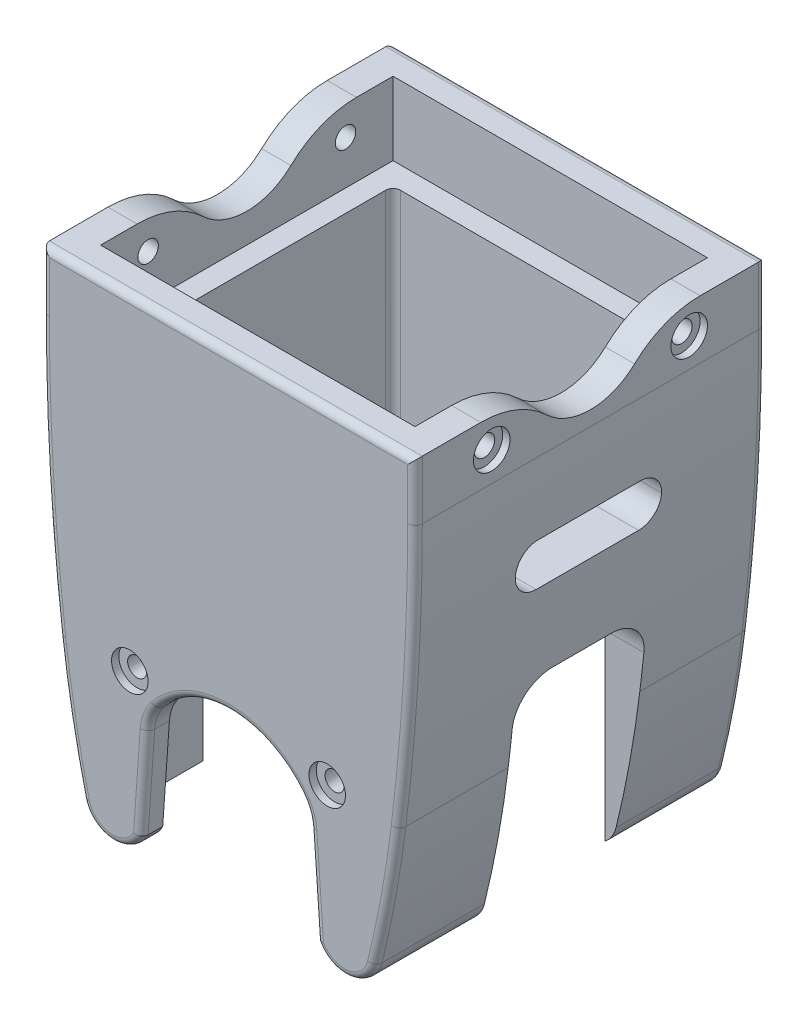
SolidWorks part; units mm, degrees
ref_plane "Front Plane" through (0, 0, 0) normal (0, 0, 1) x (1, 0, 0)
ref_plane "Top Plane" through (0, 0, 0) normal (0, 1, 0) x (1, 0, 0)
ref_plane "Right Plane" through (0, 0, 0) normal (1, 0, 0) x (0, 0, -1)
sketch "Sketch1" plane through (0, 0, 0) normal (0, 0, 1) x (1, 0, 0)
  line L0 (0, 18.8617) -> (0, -23.7037) construction
  line L1 (-12, -44.7495) -> (-11.0833, -31.7495)
  line L2 (-25.5, 18.8617) -> (0, 18.8617)
  line L7 (-25.5, 10.8617) -> (-25.5, 18.8617)
  line L10 (25.5, 10.8617) -> (25.5, 18.8617)
  line L11 (25.5, 18.8617) -> (0, 18.8617)
  line L12 (-16.2969, -47.1383) -> (16.2969, -47.1383) construction
  line L13 (11.0833, -31.7495) -> (12, -44.7495)
  arc A3 (-23.25, -26.1383) -> (-25.5, 10.8617) centre (279.8472, 10.8617) cw
  circle A14 centre (-13.5, -25.5854) radius 1.3
  arc A19 (23.25, -26.1383) -> (25.5, 10.8617) centre (-279.8472, 10.8617) ccw
  circle A20 centre (13.5, -25.5854) radius 1.3
  arc A21 (9.8042, -28.4495) -> (-9.8042, -28.4495) centre (0, -36.2037) ccw
  arc A22 (9.8042, -28.4495) -> (11.0833, -31.7495) centre (5.0982, -32.1715) cw
  arc A23 (-11.0833, -31.7495) -> (-9.8042, -28.4495) centre (-5.0982, -32.1715) cw
  arc A24 (-12, -44.7495) -> (-20, -43.9047) centre (-15.8479, -42.8869) cw
  arc A25 (-20, -43.9047) -> (-23.25, -26.1383) centre (127.6048, -7.723) cw
  arc A26 (20, -43.9047) -> (23.25, -26.1383) centre (-127.6048, -7.723) ccw
  arc A27 (12, -44.7495) -> (20, -43.9047) centre (15.8479, -42.8869) ccw
  point P2 (0, -23.7037)
  point P4 (0, 0)
  point P8 (0, 0)
  point P11 (-12.75, 18.8617)
  point P20 (-16.2969, -47.1383)
  point P34 (16.2969, -47.1383)
  dimension "D5" = 40
  dimension "D6" = 51
  dimension "D2" = 2.6
  dimension "D3" = 13
  dimension "D9" = 18.8617
  dimension "D10" = 6
  dimension "D11" = 31.6958
  dimension "D12" = 8
  dimension "D13" = 12.5
  dimension "D14" = 37
  dimension "D1" = 27
  dimension "D4" = 66
  dimension "D7" = 8
  dimension "D8" = 3.3
  dimension "D15" = 2.25
  dimension "D16" = 1.8817
extrude "Main Shape" add sketch "Sketch1" against normal mid plane 48
sketch "Sketch8" plane through (0, 0, 24) normal (0, 0, 1) x (1, 0, 0)
  circle A0 centre (-13.5, -25.5854) radius 2.5
  circle A1 centre (13.5, -25.5854) radius 2.5
  dimension "D1" = 5
extrude "Lower Mounting Counterbores" cut sketch "Sketch8" against normal blind 1
mirror "Mirror1" about plane through (0, 0, 0) normal (0, 0, 1) of "Lower Mounting Counterbores"
sketch "Sketch2" plane through (0, 18.8617, 0) normal (0, 1, 0) x (1, 0, 0)
  line L0 (25.5, 24) -> (25.5, -24) construction
  line L1 (25.5, -24) -> (-25.5, -24) construction
  line L5 (-25.5, 0) -> (25.5, 0) construction
  line L7 (0, 26) -> (0, -26) construction
  line L8 (-25.5, 24) -> (-25.5, -24) construction
  line L12 (-21.5, -20) -> (21.5, -20)
  line L13 (21.5, -20) -> (21.5, 20)
  line L14 (21.5, 20) -> (-21.5, 20)
  line L15 (-21.5, 20) -> (-21.5, -20)
  point P9 (0, 0)
  point P16 (0, 0)
  dimension "D1" = 4
  dimension "D2" = 4
extrude "Upper Herculex Cutout" cut sketch "Sketch2" against normal through all
sketch "Sketch10" plane through (0, 0, -20) normal (0, 0, 1) x (1, 0, 0)
  line L0 (-21.5, 8.8617) -> (-18.5, 8.8617)
  line L1 (-21.5, -37.1178) -> (-21.5, 18.8617) construction
  line L2 (-18.5, 8.8617) -> (-18.5, -46.2399)
  line L3 (-21.5, -37.1178) -> (-21.5, 8.8617)
  line L4 (0, 0) -> (0, 18.8617) construction
  line L5 (25.5, 18.8617) -> (-25.5, 18.8617) construction
  line L6 (21.5, -37.1178) -> (21.5, 8.8617)
  line L7 (18.5, 8.8617) -> (18.5, -46.2399)
  line L8 (21.5, 8.8617) -> (18.5, 8.8617)
  arc A0 (-20, -43.9047) -> (-12, -44.7495) centre (-15.8479, -42.8869) ccw construction
  arc A1 (-21.5, -37.1178) -> (-20, -43.9047) centre (127.6048, -7.723) ccw construction
  arc A2 (-20, -43.9047) -> (-18.5, -46.2399) centre (-15.8479, -42.8869) ccw
  arc A3 (-21.5, -37.1178) -> (-20, -43.9047) centre (127.6048, -7.723) ccw
  arc A4 (20, -43.9047) -> (18.5, -46.2399) centre (15.8479, -42.8869) cw
  arc A5 (21.5, -37.1178) -> (20, -43.9047) centre (-127.6048, -7.723) cw
  dimension "D1" = 3
  dimension "D2" = 10
extrude "Boss-Extrude3" add sketch "Sketch10" along normal up to surface (40 mm away) up to face at (0, -27.9099, 20)
sketch "Sketch12" plane through (0, 8.8617, 0) normal (0, 1, 0) x (1, 0, 0)
  line L0 (18.5, -20) -> (18.5, 20) construction
  line L1 (-18.5, 20) -> (18.5, 20)
  line L2 (-18.5, 20) -> (-18.5, 17)
  line L3 (-18.5, 17) -> (18.5, 17)
  line L4 (18.5, 20) -> (18.5, 17)
  line L6 (-18.5, -20) -> (18.5, -20)
  line L7 (-18.5, -20) -> (-18.5, -17)
  line L8 (-18.5, -17) -> (18.5, -17)
  line L9 (18.5, -20) -> (18.5, -17)
  dimension "D1" = 3
extrude "Boss-Extrude4" add sketch "Sketch12" against normal blind 28
sketch "Sketch15" plane through (0, -19.1383, 0) normal (0, -1, 0) x (1, 0, 0)
  line L1 (-18.5, 21) -> (18.5, 21)
  line L2 (-18.5, 21) -> (-18.5, -21)
  line L3 (-18.5, -21) -> (18.5, -21)
  line L4 (18.5, 21) -> (18.5, -21)
  line L5 (-18.5, 21) -> (18.5, -21) construction
  line L6 (-18.5, -21) -> (18.5, 21) construction
  line L7 (18.5, 20) -> (18.5, -20) construction
  line L8 (-18.5, 20) -> (18.5, 20) construction
  point P0 (0, 0)
  dimension "D1" = 1
extrude "Lower Herculex Cutout" cut sketch "Sketch15" along normal through all
sketch "Sketch3" plane through (25.5, 0, 0) normal (1, 0, 0) x (0, 0, -1)
  line L8 (0, 0) -> (0, 18.8617) construction
  line L10 (-15, 18.8617) -> (15, 18.8617)
  line L11 (24, 18.8617) -> (-24, 18.8617) construction
  line L12 (24, 18.8617) -> (-24, 18.8617) construction
  line L13 (0, 0) -> (0, -16.2399) construction
  arc A0 (-6.0345, 15.2755) -> (-15, 18.8617) centre (-15, 5.8617) ccw
  arc A1 (-6.0345, 15.2755) -> (0, 12.8617) centre (0, 21.6117) ccw
  arc A2 (6.0345, 15.2755) -> (0, 12.8617) centre (0, 21.6117) cw
  arc A3 (6.0345, 15.2755) -> (15, 18.8617) centre (15, 5.8617) cw
  dimension "D3" = 13
  dimension "D1" = 30
  dimension "D2" = 6
extrude "HerculeX Cutout" cut sketch "Sketch3" against normal through all both and the other way through all
sketch "Sketch11" plane through (25.5, 0, 0) normal (1, 0, 0) x (0, 0, -1)
  line L0 (-9, -46.2399) -> (9, -46.2399)
  line L1 (-21, -46.2399) -> (21, -46.2399) construction
  line L2 (-9, -46.2399) -> (-9, -21.2399)
  line L3 (-4, -16.2399) -> (4, -16.2399)
  line L4 (9, -21.2399) -> (9, -46.2399)
  arc A0 (4, -16.2399) -> (9, -21.2399) centre (4, -21.2399) cw
  arc A1 (-9, -21.2399) -> (-4, -16.2399) centre (-4, -21.2399) cw
  point P5 (0, -46.2399)
  point P8 (0, -46.2399)
  point P12 (-9, -16.2399)
  dimension "D3" = 5
  dimension "D1" = 18
  dimension "D2" = 30
extrude "Cable Cutout" cut sketch "Sketch11" against normal through all
sketch "Sketch14" plane through (25.5, 0, 0) normal (1, 0, 0) x (0, 0, -1)
  line L0 (24, 10.8617) -> (-24, 10.8617) construction
  line L1 (-10, -5.1383) -> (10, -5.1383)
  line L2 (-10, -5.1383) -> (-10, 0.8617)
  line L3 (-10, 0.8617) -> (10, 0.8617)
  line L4 (10, -5.1383) -> (10, 0.8617)
  line L5 (-10, -5.1383) -> (10, 0.8617) construction
  line L6 (-10, 0.8617) -> (10, -5.1383) construction
  point P0 (0, -2.1383)
  dimension "D1" = 6
  dimension "D2" = 20
  dimension "D3" = 10
extrude "Cut-Extrude1" cut sketch "Sketch14" against normal up to next
sketch "Sketch5" plane through (-25.5, 0, 0) normal (-1, 0, 0) x (0, 0, 1)
  line L0 (0, 21.3905) -> (0, 0) construction
  circle A0 centre (-13.5, 14.8617) radius 1.4
  circle A1 centre (-13.5, 14.8617) radius 2.5
  circle A2 centre (13.5, 14.8617) radius 1.4
  circle A3 centre (13.5, 14.8617) radius 2.5
  dimension "D1" = 2.8
  dimension "D2" = 5
  dimension "D3" = 27
  dimension "D4" = 4
extrude "2.6mm Thru Hole2" cut sketch "Sketch5" against normal up to next and the other way through all contours A0 | A2 region at (-25.5, 14.8617, -13.5) region at (-25.5, 14.8617, 13.5)
extrude "1mm Counterbore1" cut sketch "Sketch5<3>" against normal blind 1
sketch "Sketch5<3>" plane through (-25.5, 0, 0) normal (-1, 0, 0) x (0, 0, 1) same geometry as "Sketch5"
sketch "Sketch7" plane through (25.5, 0, 0) normal (1, 0, 0) x (0, 0, -1)
  circle A0 centre (-13.5, 14.8617) radius 1.4
  circle A1 centre (13.5, 14.8617) radius 1.4
  circle A2 centre (-13.5, 14.8617) radius 1.4 construction
  circle A3 centre (13.5, 14.8617) radius 1.4 construction
  circle A4 centre (-13.5, 14.8617) radius 2.5
  circle A5 centre (13.5, 14.8617) radius 2.5
  circle A6 centre (13.5, 14.8617) radius 2.5 construction
  circle A7 centre (-13.5, 14.8617) radius 2.5 construction
extrude "2.6mm Thru Hole3" cut sketch "Sketch7" against normal up to next contours A0 | A1 region at (25.5, 14.8617, 13.5) region at (25.5, 14.8617, -13.5)
extrude "1mm Counterbore2" cut sketch "Sketch7<3>" against normal blind 1
sketch "Sketch7<3>" plane through (25.5, 0, 0) normal (1, 0, 0) x (0, 0, -1) same geometry as "Sketch7"
fillet "Fillet4" radius 3 4 edges at (21.7903, -5.1383, 10) (21.9181, 0.8617, 10) (21.9181, 0.8617, -10) (21.7903, -5.1383, -10)
fillet "Fillet3" radius 5 4 edges at (18.5, -19.1383, 19) (-18.5, -19.1383, 19) (18.5, -19.1383, -19) (-18.5, -19.1383, -19)
fillet "Fillet2" radius 1 32 edges at (25.5, 14.8617, -24) (24.937, -7.6725, -24) (21.8892, -35.0698, -24) (11.5416, -38.2495, -24) (10.6926, -30.003, -24) (0, -23.7037, -24) (-10.6926, -30.003, -24) (25.5, 14.8617, 24) (24.937, -7.6725, 24) (21.8892, -35.0698, 24) (11.5416, -38.2495, 24) (10.6926, -30.003, 24) (0, -23.7037, 24) (-10.6926, -30.003, 24) (0, 18.8617, -24) (16.2969, -47.1383, -24) (-11.5416, -38.2495, -24) (-16.2969, -47.1383, -24) (-21.8892, -35.0698, -24) (-24.937, -7.6725, -24) (-25.5, 14.8617, -24) (0, 18.8617, 24) (16.2969, -47.1383, 24) (-11.5416, -38.2495, 24) (-16.2969, -47.1383, 24) (-21.8892, -35.0698, 24) (-25.5, 14.8617, 24) (-24.937, -7.6725, 24) (18.5, -7.6383, -17) (-18.5, -7.6383, -17) (-18.5, -7.6383, 17) (18.5, -7.6383, 17)
